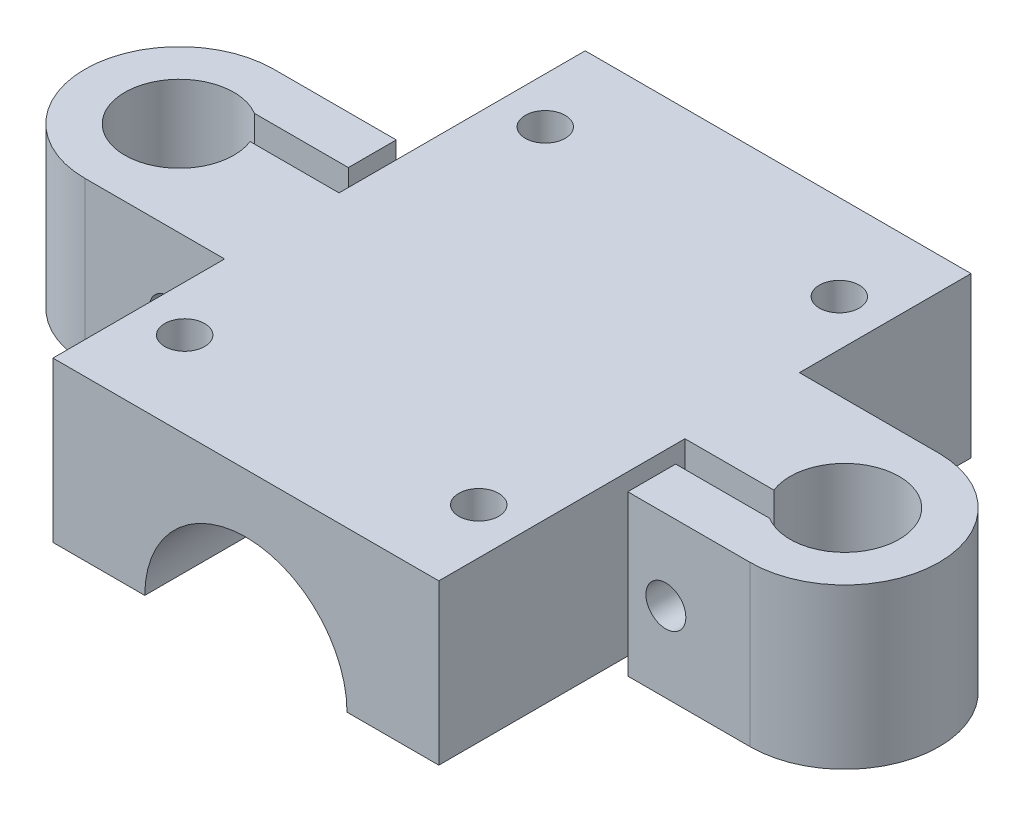
SolidWorks part; units mm, degrees
ref_plane "Front Plane" through (0, 0, 0) normal (1, 0, 0) x (0, 1, 0)
ref_plane "Top Plane" through (0, 0, 0) normal (0, 0, 1) x (0, 1, 0)
ref_plane "Right Plane" through (0, 0, 0) normal (0, 1, 0) x (-1, 0, 0)
sketch "Sketch1" plane through (0, 0, 0) normal (0, 0, 1) x (0, 1, 0)
  line L0 (0, -6.9) -> (0, -14.5) construction
  line L1 (0, 0) -> (12, 0)
  line L2 (0, 0) -> (0, -6.9)
  line L3 (0, -29) -> (12, -29)
  line L4 (12, 0) -> (12, -29)
  line L5 (6, -29) -> (6, 0) construction
  line L6 (0, -14.5) -> (12, -14.5) construction
  line L7 (0, -22.1) -> (0, -29)
  line L8 (0, -14.5) -> (0, -22.1) construction
  arc A0 (0, -22.1) -> (0, -6.9) centre (0, -14.5) ccw
  arc A1 (0, -6.9) -> (0, -22.1) centre (0, -14.5) ccw construction
  point P428 (6, -14.5)
  dimension "D3" = 15.2
  dimension "D1" = 29
  dimension "D2" = 12
extrude "Boss-Extrude1" add sketch "Sketch1" along normal blind 20 and the other way blind 20 contours A0 L7 L3 L4 L1 L2 region at (0.3138, 6, 0)
sketch "Sketch3" plane through (0, 12, 0) normal (0, 1, 0) x (-1, 0, 0)
  line L0 (0, 0) -> (-29, 0) construction
  line L1 (0, -20) -> (0, 20) construction
  line L2 (-29, -20) -> (-29, 20) construction
  line L3 (10.5, 0) -> (-39.5, 0) construction
  line L4 (10.5, -7.1) -> (-39.5, -7.1)
  line L5 (10.5, 7.1) -> (-39.5, 7.1)
  line L6 (-14.5, 20) -> (-14.5, -20) construction
  line L7 (0, 20) -> (-29, 20) construction
  line L8 (0, -20) -> (-29, -20) construction
  line L9 (1.3, -7.1) -> (1.3, -3.5)
  line L10 (1.3, -3.5) -> (8.3646, -3.5)
  line L11 (6.6842, -1.5) -> (0, -1.5)
  line L12 (0, -1.5) -> (0, -7.1)
  line L13 (0, -7.1) -> (1.3, -7.1)
  line L14 (-30.3, 7.1) -> (-30.3, 3.5)
  line L15 (-30.3, 3.5) -> (-37.3646, 3.5)
  line L16 (-35.6842, 1.5) -> (-29, 1.5)
  line L17 (-29, 1.5) -> (-29, 7.1)
  line L18 (-29, 7.1) -> (-30.3, 7.1)
  arc A0 (10.5, -7.1) -> (10.5, 7.1) centre (10.5, 0) ccw
  arc A1 (-39.5, 7.1) -> (-39.5, -7.1) centre (-39.5, 0) ccw
  arc A2 (-37.3646, 3.5) -> (-35.6842, 1.5) centre (-39.5, 0) ccw
  arc A3 (8.3646, -3.5) -> (6.6842, -1.5) centre (10.5, 0) ccw
  arc A4 (6.6842, -1.5) -> (8.3646, -3.5) centre (10.5, 0) ccw construction
  arc A5 (-35.6842, 1.5) -> (-37.3646, 3.5) centre (-39.5, 0) ccw construction
  point P9 (-14.5, 0)
  point P22 (-14.5, 0)
  point P33 (-30.7716, 3.226)
  line M6 (0, -20) -> (0, 20)
  line M8 (-29, 20) -> (-29, -20)
  dimension "D3" = 8.2
  dimension "D4" = 50
  dimension "D5" = 2
  dimension "D7" = 1.5
  dimension "D8" = 1.3
  dimension "D9" = 2
  dimension "D10" = 1.5
extrude "Boss-Extrude2" add sketch "Sketch3" against normal up to surface (12 mm away) contours A3 L10 L9 L4 A0 L5 L11 M6 | A2 L15 L14 L5 A1 L4 L16 M8 region at (-5.9, 12, -6.8739) region at (34.25, 12, -6.8739) up to face at (3.45, 0, 0)
sketch "Sketch4" plane through (0, 0, -1.5) normal (0, 0, -1) x (1, 0, 0)
  line L0 (-6.6842, -6) -> (0, -6) construction
  line L1 (-6.6842, 0) -> (-6.6842, -12) construction
  circle A0 centre (-4.1642, -6) radius 1.5
  point P6 (-2.7822, -6)
  point P7 (-4.1622, -6)
  point P8 (-4.1622, -6)
  dimension "screw_hole" = 3
  dimension "D1" = 2.52
extrude "Cut-Extrude1" cut sketch "Sketch4" against normal through all and the other way through all contours A0 L0 | L0 A0 region at (-4.1642, 5.3634, -1.5) region at (-4.1642, 6.6366, -1.5)
sketch "Sketch5" plane through (0, 0, 1.5) normal (0, 0, 1) x (1, 0, 0)
  line L0 (35.6842, 6) -> (29, 6) construction
  line L1 (35.6842, 0) -> (35.6842, 12) construction
  line L2 (29, 0) -> (29, 12) construction
  circle A0 centre (33.1642, 6) radius 1.5
  dimension "D2" = 2.52
extrude "Cut-Extrude2" cut sketch "Sketch5" against normal through all and the other way through all contours L0 A0 | A0 L0 region at (33.1642, 5.3634, 1.5) region at (33.1642, 6.6366, 1.5)
sketch "Sketch7" plane through (0, 0, 0) normal (0, -1, 0) x (1, 0, 0)
  line L0 (0, 20) -> (6.9, 7.1) construction
  line L1 (6.9, -20) -> (6.9, 20) construction
  line L2 (0, 7.1) -> (6.9, 20) construction
  line L3 (29, -7.1) -> (22.1, -20) construction
  line L4 (29, -20) -> (22.1, -7.1) construction
  line L5 (22.1, -20) -> (22.1, 20) construction
  line L6 (0, -20) -> (6.9, -7.1) construction
  line L7 (6.9, -20) -> (0, -7.1) construction
  line L9 (22.1, 20) -> (29, 7.1) construction
  line L10 (29, 1.5) -> (29, 20) construction
  line L11 (29, 20) -> (22.1, 7.1) construction
  line L12 (0, -20) -> (0, -1.5) construction
  circle A0 centre (3.45, 13.55) radius 1.5
  circle A1 centre (25.55, -13.55) radius 1.5
  circle A2 centre (25.55, 13.55) radius 1.5
  circle A3 centre (3.45, -13.55) radius 1.5
  dimension "D3" = 12.9
  dimension "D4" = 12.9
  dimension "x_hole_offset" = 12.9
  dimension "D6" = 12.9
extrude "Cut-Extrude3" cut sketch "Sketch7" against normal through all
equation "\"D2@Sketch3\"=\"D1@Sketch3\""
equation "\"D8@Sketch3\"=\"D6@Sketch3\""
equation "\"D9@Sketch3\"=\"D5@Sketch3\""
equation "\"D10@Sketch3\"=\"D7@Sketch3\""
equation "\"screw_hole\"= 3mm"
equation "\"offset\"= 2.52mm"
equation "\"screw_hole@Sketch4\"=\"screw_hole\""
equation "\"D1@Sketch4\"=\"offset\""
equation "\"D1@Sketch5\"=\"screw_hole\""
equation "\"D2@Sketch5\"=\"offset\""
equation "\"D1@Sketch7\"=\"screw_hole\""
equation "\"D4@Sketch7\"=\"D3@Sketch7\""
equation "\"y_length\" = 40mm"
equation "\"z_breadth\"= 29mm"
equation "\"D1@Boss-Extrude1\"=\"y_length\"/2"
equation "\"D2@Boss-Extrude1\"=\"y_length\"/2"
equation "\"D1@Sketch1\"=\"z_breadth\""
equation "\"lm8uu_bearing_dia\"= 15.2mm"
equation "\"D3@Sketch1\"= \"lm8uu_bearing_dia\""
